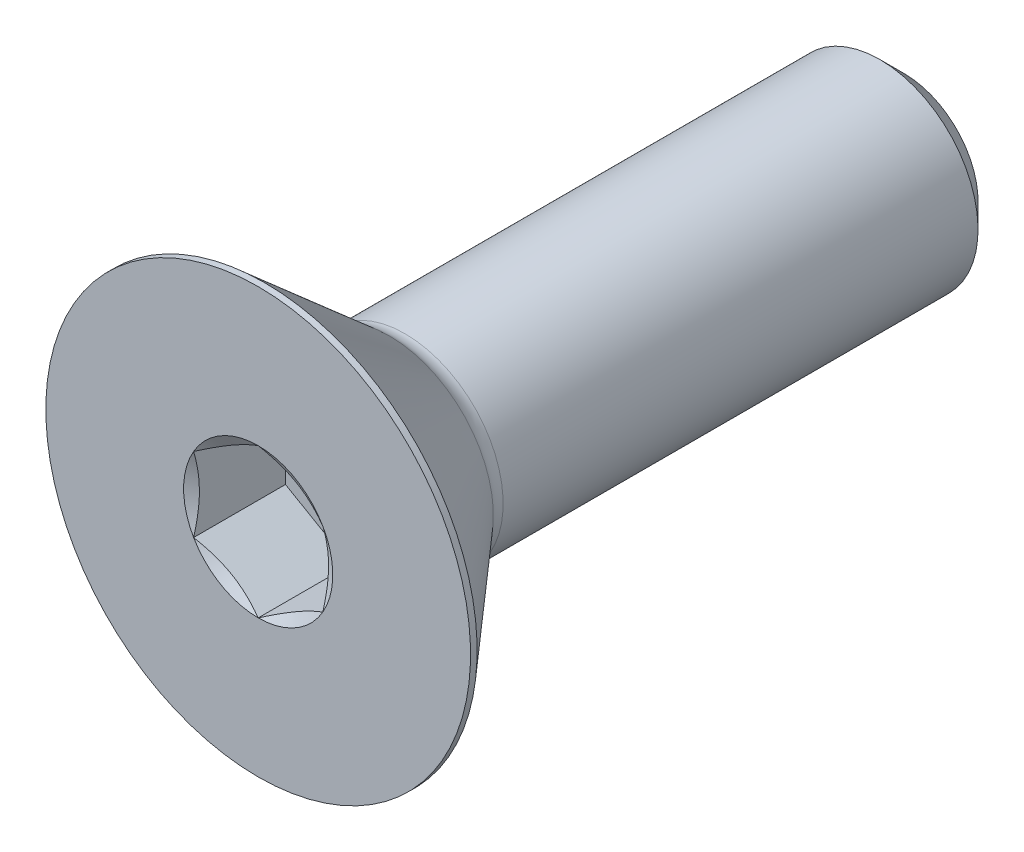
SolidWorks part; units mm, degrees
material "Plain Carbon Steel"
ref_plane "Front" through (0, 0, 0) normal (0, 0, 1) x (1, 0, 0)
ref_plane "Top" through (0, 0, 0) normal (0, 1, 0) x (1, 0, 0)
ref_plane "Right" through (0, 0, 0) normal (1, 0, 0) x (0, 0, -1)
sketch "Sketch1" plane through (0, 0, 0) normal (1, 0, 0) x (0, 0, -1)
  line L0 (0, 5.2197) -> (0.1613, 5.2197) construction
  line L1 (0.1613, 5.2197) -> (3.2258, 2.5558) construction
  line L2 (0, 2.413) -> (15.875, 2.413)
  line L3 (15.875, 2.413) -> (15.875, 0)
  line L4 (15.875, 0) -> (0, 0)
  line L5 (0, 0) -> (0, 5.2197) construction
  line L6 (0, 5.2197) -> (0, -5.2197) construction
  line L7 (15.875, 2.413) -> (15.875, -2.413) construction
  line L8 (0, -5.2197) -> (0.1613, -5.2197) construction
  line L9 (0.1613, -5.2197) -> (3.2258, -2.5558) construction
  line L11 (0, 2.413) -> (0, 0)
  line L12 (3.6076, 2.413) -> (3.6076, 0) construction
  line L13 (-9.525, 0) -> (-9.525, 2.413) construction
  arc A1 (3.2258, 2.5558) -> (3.6076, 2.413) centre (3.6076, 2.995) ccw construction
  dimension "D1" = 0.1613
  dimension "Min Thread" = 25.4
revolve "Revolve1" add sketch "Sketch1" angle 360 mid plane about L4
ref_plane "Plane2" through (0, 0, 9.525) normal (0, 0, 1) x (1, 0, 0)
chamfer "Chamfer1" distance 0.5953 angle 45 1 edges at (0, 2.413, -15.875)
sketch "Sketch7" plane through (0, 0, 0) normal (1, 0, 0) x (0, 0, -1)
  line L0 (0, 5.2197) -> (0.1613, 5.2197) construction
  line L1 (0.1613, 5.2197) -> (3.2258, 2.5558) construction
  line L2 (0, 5.2197) -> (0.1613, 5.2197)
  line L3 (0.1613, 5.2197) -> (3.2258, 2.5558)
  line L4 (3.6076, 2.413) -> (3.6076, 0) construction
  line L5 (3.6076, 2.413) -> (3.6076, 0)
  line L7 (0, 0) -> (0, 5.2197) construction
  line L8 (0, 0) -> (0, 5.2197)
  line L9 (0, 0) -> (3.6076, 0)
  line L10 (5.7417, 0) -> (-5.7417, 0) construction
  arc A0 (3.2258, 2.5558) -> (3.6076, 2.413) centre (3.6076, 2.995) ccw construction
  arc A1 (3.2258, 2.5558) -> (3.6076, 2.413) centre (3.6076, 2.995) ccw
revolve "Revolve2" add sketch "Sketch7" angle 360 mid plane about L9
ref_plane "Plane1" through (0, 0, -3.6076) normal (0, 0, 1) x (1, 0, 0)
sketch "Sketch5" plane through (0, 0, 0) normal (0, 0, 1) x (1, 0, 0)
  line L0 (0, 0) -> (-1.8331, 0) construction
  line L1 (0, 0) -> (-2.7496, 1.5875) construction
  line L2 (0, 0) -> (-2.7496, -1.5875) construction
  line L6 (0, 1.8331) -> (0, 1.5119) construction
  line L7 (0, 1.5119) -> (0, 1.1906) construction
  line L9 (0, 1.8331) -> (-1.5875, 0.9165)
  line L10 (-1.5875, 0.9165) -> (-1.5875, -0.9165)
  line L11 (-1.5875, -0.9165) -> (0, -1.8331)
  line L12 (0, -1.8331) -> (1.5875, -0.9165)
  line L13 (1.5875, -0.9165) -> (1.5875, 0.9165)
  line L14 (1.5875, 0.9165) -> (0, 1.8331)
  circle A0 centre (0, 0) radius 1.8331 construction
  circle A1 centre (0, 0) radius 1.5119 construction
  circle A2 centre (0, 0) radius 1.1906 construction
  circle A3 centre (0, 0) radius 1.5875 construction
  dimension "D3" = 2.3813
  dimension "D4" = 30
  dimension "D5" = 30
extrude "Cut-Extrude2" cut sketch "Sketch5" against normal blind 2.2581
sketch "Sketch6" plane through (0, 0, 0) normal (0, 0, 1) x (1, 0, 0)
  circle A0 centre (0, 0) radius 1.8331
extrude "Cut-Extrude3" cut sketch "Sketch6" against normal blind 2.2581 draft 60
sketch "Sketch9" [suppressed] plane through (0, 0, -3.6076) normal (0, 0, 1) x (1, 0, 0)
  circle A1 centre (0, 0) radius 2.413
  circle A2 centre (0, 0) radius 2.413
  point P0 (0, 2.413)
  dimension "D1" = 0
extrude "Boss-Extrude2" [suppressed] add sketch "Sketch9" against normal up to surface (15.4424 mm away) up to plane "Plane2"
move or copy body "Body-Move/Copy1" [suppressed] bodies to move or copy 113
equation "\"D1@Cut-Extrude2\" = \"Head Ht@Sketch1\" * .7"
equation "\"D1@Sketch1\" = \"Head Ht@Sketch1\" * .05"
equation "\"D1@Cut-Extrude3\" = \"D1@Cut-Extrude2\""
equation "\"D3@Sketch5\" = \"Hex@Sketch5\" * .75"
